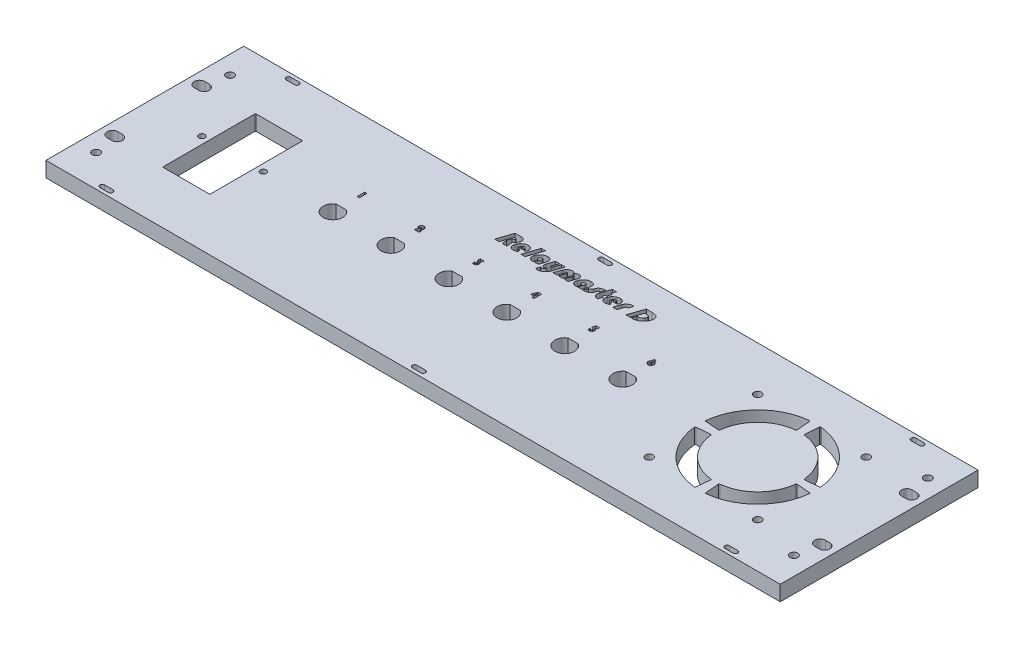
SolidWorks part; units mm, degrees
ref_plane "Front Plane" through (0, 0, 0) normal (0, 0, 1) x (1, 0, 0)
ref_plane "Top Plane" through (0, 0, 0) normal (0, 1, 0) x (1, 0, 0)
ref_plane "Right Plane" through (0, 0, 0) normal (1, 0, 0) x (0, 0, -1)
sketch "Sketch1" plane through (0, 0, 0) normal (0, 1, 0) x (1, 0, 0)
  line L0 (158.9992, 68.014) -> (158.9992, -61.986) construction
  line L1 (-82.3008, 68.014) -> (400.2992, 68.014)
  line L2 (-82.3008, 68.014) -> (-82.3008, -61.986)
  line L3 (-82.3008, -61.986) -> (400.2992, -61.986)
  line L4 (400.2992, 68.014) -> (400.2992, -61.986)
  line L5 (-82.3008, 3.014) -> (400.2992, 3.014) construction
  line L6 (-75.0008, 35.089) -> (-72.0008, 35.089)
  line L7 (-75.0008, 28.089) -> (-72.0008, 28.089)
  line L8 (-75.0008, -22.061) -> (-72.0008, -22.061)
  line L9 (-75.0008, -29.061) -> (-72.0008, -29.061)
  line L10 (392.9992, 28.089) -> (389.9992, 28.089)
  line L11 (392.9992, 35.089) -> (389.9992, 35.089)
  line L12 (392.9992, -29.061) -> (389.9992, -29.061)
  line L13 (392.9992, -22.061) -> (389.9992, -22.061)
  arc A0 (-72.0008, 35.089) -> (-72.0008, 28.089) centre (-72.0008, 31.589) cw
  arc A1 (-75.0008, 28.089) -> (-75.0008, 35.089) centre (-75.0008, 31.589) cw
  arc A2 (-72.0008, -29.061) -> (-72.0008, -22.061) centre (-72.0008, -25.561) ccw
  arc A3 (-75.0008, -22.061) -> (-75.0008, -29.061) centre (-75.0008, -25.561) ccw
  arc A4 (389.9992, 35.089) -> (389.9992, 28.089) centre (389.9992, 31.589) ccw
  arc A5 (392.9992, 28.089) -> (392.9992, 35.089) centre (392.9992, 31.589) ccw
  arc A6 (389.9992, -29.061) -> (389.9992, -22.061) centre (389.9992, -25.561) cw
  arc A7 (392.9992, -22.061) -> (392.9992, -29.061) centre (392.9992, -25.561) cw
  circle A8 centre (-70.3008, 47.014) radius 2.5527
  circle A9 centre (-70.3008, -40.986) radius 2.5527
  circle A10 centre (388.2992, -40.986) radius 2.5527
  circle A11 centre (388.2992, 47.014) radius 2.5527
  dimension "D7" = 5.1054
  dimension "D1" = 482.6
  dimension "D2" = 130
  dimension "D3" = 7
  dimension "D4" = 3
  dimension "D5" = 57.15
  dimension "D6" = 465
  dimension "D8" = 88
  dimension "D9" = 12
extrude "Boss-Extrude1" add sketch "Sketch1" along normal blind 10
sketch "Sketch2" plane through (0, 10, 0) normal (0, 1, 0) x (1, 0, 0)
  text T0 "Relaymaster D" font "Bauhaus 93" height 10
extrude "Cut-Extrude2" cut sketch "Sketch2" against normal through all
sketch "Sketch3" plane through (0, 10, 0) normal (0, 1, 0) x (-1, 0, 0)
  line L0 (24.6268, -33.514) -> (24.6268, 27.486) construction
  line L1 (40.1268, -33.514) -> (9.1268, -33.514)
  line L2 (40.1268, -33.514) -> (40.1268, 27.486)
  line L3 (40.1268, 27.486) -> (9.1268, 27.486)
  line L4 (9.1268, -33.514) -> (9.1268, 27.486)
  line L5 (40.1268, -3.014) -> (9.1268, -3.014) construction
  circle A0 centre (44.8268, -3.014) radius 2
  circle A1 centre (4.4268, -3.014) radius 2
  dimension "D3" = 4
  dimension "D1" = 31
  dimension "D2" = 61
  dimension "D4" = 40.4
extrude "Cut-Extrude3" cut sketch "Sketch3" against normal through all
fillet "Fillet1" radius 0.5 4 edges at (-40.1268, 5, 27.486) (-9.1268, 5, 27.486) (-9.1268, 5, -33.514) (-40.1268, 5, -33.514)
sketch "Sketch4" plane through (0, 10, 0) normal (0, 1, 0) x (1, 0, 0)
  line L0 (280.4889, 43.014) -> (360.4889, -36.986) construction
  line L1 (280.4889, 43.014) -> (360.4889, 43.014) construction
  line L2 (280.4889, 43.014) -> (280.4889, -36.986) construction
  line L3 (280.4889, -36.986) -> (360.4889, -36.986) construction
  line L4 (360.4889, 43.014) -> (360.4889, -36.986) construction
  line L5 (280.4889, -36.986) -> (360.4889, 43.014) construction
  line L6 (320.4889, 43.014) -> (320.4889, -36.986) construction
  line L7 (280.4889, 3.014) -> (360.4889, 3.014) construction
  line L8 (292.5954, 5.4544) -> (282.6335, 6.3259)
  line L9 (318.0485, 30.9074) -> (317.177, 40.8694)
  line L10 (292.5954, 0.5736) -> (282.6335, -0.2979)
  line L11 (348.3823, 0.5736) -> (358.3443, -0.2979)
  line L12 (348.3823, 5.4544) -> (358.3443, 6.3259)
  line L13 (400.2992, 3.014) -> (283.5023, 3.014) construction
  line L14 (322.9292, -24.8795) -> (323.8008, -34.8414)
  line L15 (318.0485, -24.8795) -> (317.177, -34.8414)
  line L16 (322.9292, 30.9074) -> (323.8008, 40.8694)
  line L17 (400.2992, -61.986) -> (400.2992, 68.014) construction
  circle A0 centre (284.8389, 38.664) radius 2.5
  circle A1 centre (356.1389, 38.664) radius 2.5
  circle A2 centre (356.1389, -32.636) radius 2.5
  circle A3 centre (284.8389, -32.636) radius 2.5
  arc A4 (282.6335, -0.2979) -> (317.177, -34.8414) centre (320.4889, 3.014) ccw
  arc A5 (292.5954, 0.5736) -> (318.0485, -24.8795) centre (320.4889, 3.014) ccw
  circle A6 centre (320.4889, 3.014) radius 17.6384 construction
  arc A7 (317.177, 40.8694) -> (282.6335, 6.3259) centre (320.4889, 3.014) ccw
  arc A8 (318.0485, 30.9074) -> (292.5954, 5.4544) centre (320.4889, 3.014) ccw
  arc A9 (348.3823, 5.4544) -> (322.9292, 30.9074) centre (320.4889, 3.014) ccw
  arc A10 (358.3443, 6.3259) -> (323.8008, 40.8694) centre (320.4889, 3.014) ccw
  arc A11 (323.8008, -34.8414) -> (358.3443, -0.2979) centre (320.4889, 3.014) ccw
  arc A12 (322.9292, -24.8795) -> (348.3823, 0.5736) centre (320.4889, 3.014) ccw
  dimension "D3" = 5
  dimension "D5" = 76
  dimension "D6" = 56
  dimension "D1" = 80
  dimension "D2" = 80
  dimension "D4" = 71.3
  dimension "D7" = 5
  dimension "D8" = 5
extrude "Cut-Extrude4" cut sketch "Sketch4" against normal through all
fillet "Fillet2" radius 0.5 16 edges at (292.5954, 5, -0.5736) (282.6335, 5, 0.2979) (318.0485, 5, 24.8795) (317.177, 5, 34.8414) (322.9292, 5, 24.8795) (323.8008, 5, 34.8414) (348.3823, 5, -0.5736) (358.3443, 5, 0.2979) (348.3823, 5, -5.4544) (358.3443, 5, -6.3259) (322.9292, 5, -30.9074) (323.8008, 5, -40.8694) (317.177, 5, -40.8694) (318.0485, 5, -30.9074) (292.5954, 5, -5.4544) (282.6335, 5, -6.3259)
sketch "Sketch5" plane through (0, 10, 0) normal (0, 1, 0) x (1, 0, 0)
  line L0 (-82.3008, 3.014) -> (150.789, 3.014) construction
  line L1 (-82.3008, 68.014) -> (-82.3008, -61.986) construction
  line L2 (37.9442, 8.489) -> (44.6688, 8.489)
  line L3 (19.5372, -3.411) -> (71.2296, -3.411) construction
  arc A0 (37.9442, 8.489) -> (44.6688, 8.489) centre (41.3065, 3.014) ccw
  dimension "D1" = 12.85
  dimension "D2" = 11.9
extrude "Cut-Extrude5" cut sketch "Sketch5" against normal blind 10
pattern_linear "LPattern1" count 6 spacing 38.1 along (1, 0, 0) of "Cut-Extrude5"
sketch "Sketch6" plane through (0, 10, 0) normal (0, 1, 0) x (1, 0, 0)
  line L0 (41.3065, 3.014) -> (41.3065, 27.7169) construction
  line L1 (79.4065, 3.014) -> (79.4065, 27.7169) construction
  line L2 (117.5065, 3.014) -> (117.5065, 27.7169) construction
  line L3 (155.6065, 3.014) -> (155.6065, 27.7169) construction
  line L4 (193.7065, 3.014) -> (193.7065, 27.7169) construction
  line L5 (231.8065, 3.014) -> (231.8065, 27.7169) construction
  line L6 (26.3149, 19.6671) -> (256.1737, 19.6671) construction
  text T0 "1" font "Bauhaus 93" height 5
  text T1 "2" font "Bauhaus 93" height 5
  text T2 "3" font "Bauhaus 93" height 5
  text T3 "4" font "Bauhaus 93" height 5
  text T4 "5" font "Bauhaus 93" height 5
  text T5 "6" font "Bauhaus 93" height 5
extrude "Cut-Extrude6" cut sketch "Sketch6" against normal through all
sketch "Sketch7" plane through (0, 10, 0) normal (0, 1, 0) x (1, 0, 0)
  line L0 (158.9992, 68.014) -> (158.9992, -61.986) construction
  line L1 (400.2992, 68.014) -> (-82.3008, 68.014) construction
  line L2 (-82.3008, -61.986) -> (400.2992, -61.986) construction
  line L3 (-82.3008, 3.014) -> (400.2992, 3.014) construction
  line L4 (-82.3008, 68.014) -> (-82.3008, -61.986) construction
  line L5 (400.2992, -61.986) -> (400.2992, 68.014) construction
  line L6 (161.7492, 65.799) -> (156.2492, 65.799)
  line L7 (161.7492, 62.729) -> (156.2492, 62.729)
  line L8 (161.7492, -56.701) -> (156.2492, -56.701)
  line L9 (161.7492, -59.771) -> (156.2492, -59.771)
  arc A0 (156.2492, 62.729) -> (156.2492, 65.799) centre (156.2492, 64.264) cw
  arc A1 (161.7492, 62.729) -> (161.7492, 65.799) centre (161.7492, 64.264) ccw
  arc A2 (161.7492, -56.701) -> (161.7492, -59.771) centre (161.7492, -58.236) cw
  arc A3 (156.2492, -56.701) -> (156.2492, -59.771) centre (156.2492, -58.236) ccw
  point P14 (158.9992, 65.799)
  point P20 (158.9992, 62.729)
  dimension "D1" = 3.07
  dimension "D2" = 5.5
  dimension "D3" = 122.5
extrude "Cut-Extrude7" cut sketch "Sketch7" against normal through all
pattern_linear "LPattern2" count 2 spacing 205.4 along (-1, 0, 0) of "Cut-Extrude7"
pattern_linear "LPattern3" count 2 spacing 205.4 along (1, 0, 0) of "Cut-Extrude7"
